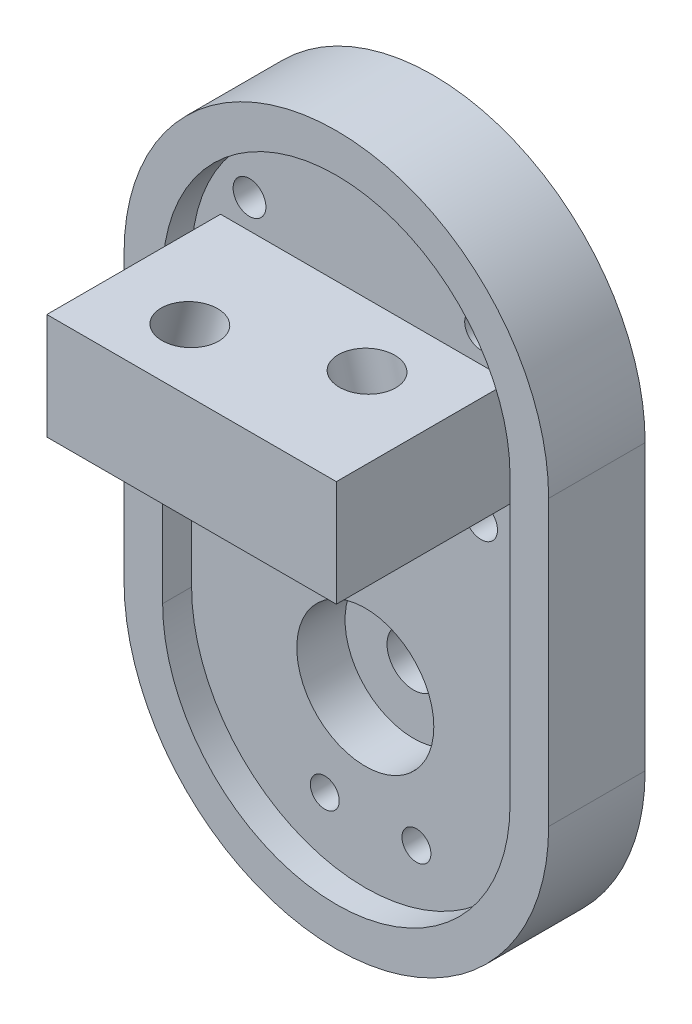
SolidWorks part; units mm, degrees
material "PET"
ref_plane "Front Plane" through (0, 0, 0) normal (0, 0, 1) x (1, 0, 0)
ref_plane "Top Plane" through (0, 0, 0) normal (0, 1, 0) x (1, 0, 0)
ref_plane "Right Plane" through (0, 0, 0) normal (1, 0, 0) x (0, 0, -1)
sketch "Sketch1" plane through (0, 0, 0) normal (0, 0, 1) x (1, 0, 0)
  line L0 (-28.5595, -15.5114) -> (-19.3326, -32.5)
  line L1 (28.5595, -15.5114) -> (19.3326, -32.5)
  line L2 (0, 0) -> (0, -22) construction
  arc A0 (28.5595, -15.5114) -> (-28.5595, -15.5114) centre (0, 0) ccw
  arc A1 (-19.3326, -32.5) -> (19.3326, -32.5) centre (0, -22) ccw
  dimension "D1" = 65
  dimension "D2" = 22
  dimension "D3" = 44
extrude "Boss-Extrude1" add sketch "Sketch1" along normal blind 7
sketch "Sketch2" plane through (0, 0, 7) normal (0, 0, 1) x (1, 0, 0)
  line L0 (0, 0) -> (0, -22) construction
  circle A0 centre (0, -22) radius 2.75
  dimension "D1" = 22
  dimension "D2" = 5.5
extrude "Cut-Extrude1" cut sketch "Sketch2" against normal through all
sketch "Sketch3" plane through (0, 0, 7) normal (0, 0, 1) x (1, 0, 0)
  circle A0 centre (0, -22) radius 7.1
  dimension "D1" = 14.2
extrude "Cut-Extrude2" cut sketch "Sketch3" against normal blind 5
sketch "Sketch6" plane through (0, 0, 7) normal (0, 0, 1) x (1, 0, 0)
  line L0 (-12, 15.95) -> (-12, -1.05) construction
  line L1 (-12, -1.05) -> (12, -1.05) construction
  line L2 (-12, 15.95) -> (12, 15.95) construction
  circle A0 centre (-12, 15.95) radius 1.7
  circle A1 centre (12, 15.95) radius 1.7
  circle A2 centre (-12, -1.05) radius 1.7
  circle A3 centre (12, -1.05) radius 1.7
  dimension "D1" = 3.4
  dimension "D2" = 3.4
  dimension "D3" = 3.4
  dimension "D4" = 3.4
  dimension "D6" = 15.95
  dimension "D5" = 12
  dimension "D7" = 24
  dimension "D8" = 24
  dimension "D9" = 17
extrude "Cut-Extrude3" cut sketch "Sketch6" against normal up to next
sketch "Sketch9" plane through (0, 0, 7) normal (0, 0, 1) x (1, 0, 0)
  line L0 (-12, -1.05) -> (12, 15.95) construction
  line L2 (15, 12.95) -> (-15, 12.95)
  line L3 (15, 12.95) -> (15, 1.95)
  line L4 (15, 1.95) -> (-15, 1.95)
  line L5 (-15, 12.95) -> (-15, 1.95)
  line L6 (15, 12.95) -> (-15, 1.95) construction
  line L7 (15, 1.95) -> (-15, 12.95) construction
  point P4 (0, 7.45)
  dimension "D1" = 30
  dimension "D2" = 11
extrude "Boss-Extrude2" add sketch "Sketch9" along normal blind 18
ref_plane "Plane1" through (0, 0, 18.5) normal (0, 0, 1) x (1, 0, 0)
sketch "Sketch10" plane through (0, 0, 18.5) normal (0, 0, 1) x (1, 0, 0)
  line L0 (-14.9719, -17.9883) -> (-6.682, 12.95) construction
  line L1 (15, 12.95) -> (-15, 12.95) construction
  line L2 (0, -22) -> (0, 1.95) construction
  line L3 (-15, 1.95) -> (15, 1.95) construction
  line L4 (-10.3649, -0.7948) -> (-6.4826, 13.6941)
  line L6 (-9.2602, 7.1914) -> (-11.3308, -0.536)
  line L7 (-10.3649, -0.7948) -> (-11.3308, -0.536)
  line L8 (-9.2602, 7.1914) -> (-11.0713, 7.6767)
  line L9 (-11.0713, 7.6767) -> (-9.2596, 14.4382)
  line L10 (-9.2596, 14.4382) -> (-6.4826, 13.6941)
  line L11 (-6.4826, 13.6941) -> (-3.7055, 12.95) construction
  circle A0 centre (0, -22) radius 15.5 construction
  dimension "D1" = 31
  dimension "D2" = 15
  dimension "D3" = 7
  dimension "D4" = 2.875
  dimension "D5" = 1
  dimension "D6" = 2.875
  dimension "D7" = 15
revolve "Cut-Revolve1" cut sketch "Sketch10" angle 360 about L4
ref_plane "Plane2" through (0, 0, 13.5) normal (0, 0, 1) x (1, 0, 0)
sketch "Sketch11" plane through (0, 0, 13.5) normal (0, 0, 1) x (1, 0, 0)
  line L0 (10.3649, -0.7948) -> (6.682, 12.95) construction
  line L1 (15, 12.95) -> (-15, 12.95) construction
  line L2 (0, -22) -> (0, 12.95) construction
  line L3 (10.3649, -0.7948) -> (6.4826, 13.6941)
  line L4 (6.4826, 13.6941) -> (3.7055, 12.95)
  line L5 (3.7055, 12.95) -> (5.5173, 6.1885)
  line L6 (5.5173, 6.1885) -> (7.3284, 6.6738)
  line L7 (7.3284, 6.6738) -> (9.3989, -1.0536)
  line L8 (9.3989, -1.0536) -> (10.3649, -0.7948)
  line L9 (15, 12.95) -> (-15, 12.95) construction
  circle A0 centre (0, -22) radius 15.5 construction
  dimension "D1" = 31
  dimension "D2" = 15
  dimension "D3" = 2.875
  dimension "D4" = 1
  dimension "D5" = 7
  dimension "D6" = 15
revolve "Cut-Revolve2" cut sketch "Sketch11" angle 360 about L3
sketch "Sketch12" plane through (0, 0, 0) normal (0, 0, -1) x (-1, 0, 0)
  line L0 (-5.3, -33.55) -> (4.2, -33.55) construction
  circle A0 centre (-5.3, -33.55) radius 1.5
  circle A1 centre (4.2, -33.55) radius 1.5
  circle A2 centre (0, -22) radius 2.75 construction
  dimension "D1" = 9.5
  dimension "D2" = 4.2
  dimension "D4" = 3
  dimension "D5" = 3
  dimension "D3" = 11.55
extrude "Cut-Extrude5" cut sketch "Sketch12" against normal through all
chamfer "Chamfer2" distance 1 angle 45 2 edges at (-5.7, -33.55, 0) (3.8, -33.55, 0)
ref_axis "Axis1" through (0, -22, 2) along (0, 0, 1)
sketch "Sketch13" plane through (0, 0, 0) normal (1, 0, 0) x (0, 0, -1)
  line L0 (-25, 1.95) -> (-7, -6)
  line L1 (-7, 32.5) -> (-7, -15.5114) construction
  line L2 (-7, -6) -> (-7, 1.95)
  line L3 (-7, 1.95) -> (-25, 1.95)
  line L5 (-2, -22) -> (-7, -22) construction
  dimension "D1" = 16
extrude "Boss-Extrude3" add sketch "Sketch13" along normal mid plane 10
sketch "Sketch14" plane through (0, 0, 7) normal (0, 0, 1) x (1, 0, 0)
  line L0 (-12, -1.05) -> (12, 15.95) construction
  line L1 (-22, 7.45) -> (-22, -22)
  line L2 (22, -22) -> (22, 7.45)
  line L3 (-28.5595, -15.5114) -> (-19.3326, -32.5)
  line L4 (28.5595, -15.5114) -> (19.3326, -32.5)
  arc A0 (19.3326, -32.5) -> (22, -22) centre (0, -22) ccw
  arc A2 (22, 7.45) -> (-22, 7.45) centre (0, 7.45) ccw
  arc A3 (28.5595, -15.5114) -> (-28.5595, -15.5114) centre (0, 0) ccw
  arc A4 (-22, -22) -> (-19.3326, -32.5) centre (0, -22) ccw
  dimension "D1" = 44
extrude "Cut-Extrude6" cut sketch "Sketch14" against normal through all
sketch "Sketch15" plane through (0, 0, 7) normal (0, 0, 1) x (1, 0, 0)
  line L0 (-22, 7.45) -> (-22, -22)
  line L1 (22, 7.45) -> (22, -22)
  line L2 (-18, 7.45) -> (-18, -22)
  line L3 (18, 7.45) -> (18, -22)
  arc A0 (-22, -22) -> (22, -22) centre (0, -22) ccw
  arc A1 (22, 7.45) -> (-22, 7.45) centre (0, 7.45) ccw
  arc A2 (22, 7.45) -> (-22, 7.45) centre (0, 7.45) ccw construction
  arc A3 (-22, -22) -> (22, -22) centre (0, -22) ccw construction
  arc A4 (-18, -22) -> (18, -22) centre (0, -22) ccw
  arc A5 (18, 7.45) -> (-18, 7.45) centre (0, 7.45) ccw
  dimension "D1" = 4
extrude "Boss-Extrude4" add sketch "Sketch15" along normal blind 3
